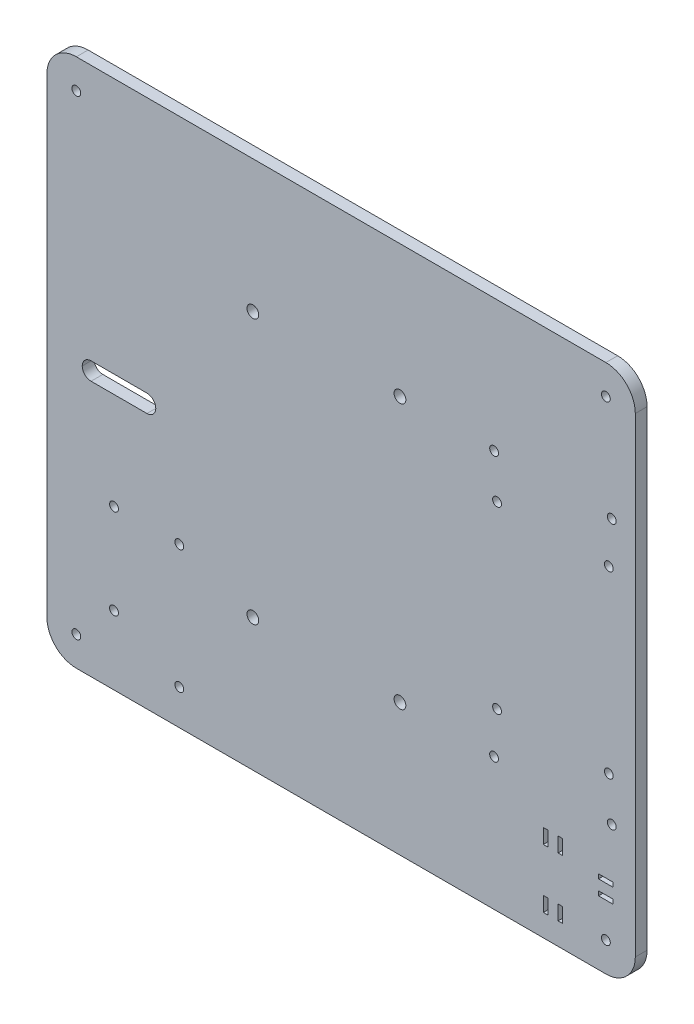
SolidWorks part; units mm, degrees
ref_plane "Front Plane" through (0, 0, 0) normal (0, 0, 1) x (1, 0, 0)
ref_plane "Top Plane" through (0, 0, 0) normal (0, 1, 0) x (1, 0, 0)
ref_plane "Right Plane" through (0, 0, 0) normal (1, 0, 0) x (0, 0, -1)
sketch "Sketch1" plane through (0, 0, 0) normal (0, 0, 1) x (1, 0, 0)
  line L0 (0, 0) -> (121.7014, 0) construction
  line L2 (105, 90) -> (-95, 90)
  line L3 (105, 90) -> (105, -90)
  line L4 (105, -90) -> (-95, -90)
  line L5 (-95, 90) -> (-95, -90)
  line L6 (105, 90) -> (-95, -90) construction
  line L7 (105, -90) -> (-95, 90) construction
  arc A0 (-28.7189, 34.6443) -> (-28.7189, -34.6443) centre (0, 0) ccw construction
  point P3 (5, 0)
  dimension "D1" = 180
  dimension "D2" = 50
  dimension "D3" = 53
  dimension "D4" = 200
extrude "Boss-Extrude1" add sketch "Sketch1" along normal blind 4
sketch "Sketch2" plane through (0, 0, 0) normal (0, 0, -1) x (-1, 0, 0)
  circle A0 centre (25, 45) radius 2 construction
  circle A1 centre (25, 45) radius 2
  circle A2 centre (-25, 45) radius 2 construction
  circle A3 centre (-25, 45) radius 2
  circle A4 centre (-25, -45) radius 2 construction
  circle A5 centre (-25, -45) radius 2
  circle A6 centre (25, -45) radius 2 construction
  circle A7 centre (25, -45) radius 2
extrude "Cut-Extrude1" cut sketch "Sketch2" against normal through all
fillet "Fillet1" radius 10 4 edges at (-95, -90, 2) (-95, 90, 2) (105, -90, 2) (105, 90, 2)
sketch "Sketch4" plane through (0, 0, 0) normal (0, 0, -1) x (-1, 0, 0)
  line L0 (-102, 0) -> (-52, 0) construction
  line L2 (-96, -30.5) -> (-58, -30.5) construction
  line L3 (-96, -30.5) -> (-96, 30.5) construction
  line L4 (-52, -36) -> (-52, 36)
  line L5 (-52, 36) -> (-102, 36)
  line L6 (-102, 36) -> (-102, -36)
  line L7 (-102, -36) -> (-52, -36)
  line L8 (-52, -36) -> (-52, 36) construction
  line L9 (-52, 36) -> (-102, 36) construction
  line L10 (-102, 36) -> (-102, -36) construction
  line L11 (-102, -36) -> (-52, -36) construction
  line L12 (-96, 30.5) -> (-58, 30.5) construction
  line L13 (-58, -30.5) -> (-58, 30.5) construction
  line L14 (-96, -30.5) -> (-58, 30.5) construction
  line L15 (-96, 30.5) -> (-58, -30.5) construction
  circle A0 centre (-96, 30.5) radius 1.5
  circle A1 centre (-58, 30.5) radius 1.5
  circle A2 centre (-96, -30.5) radius 1.5
  circle A3 centre (-58, -30.5) radius 1.5
  point P6 (-77, 0)
  dimension "D4" = 3
  dimension "D2" = 38
  dimension "D3" = 61
  dimension "D1" = 0
extrude "Cut-Extrude3" cut sketch "Sketch4" against normal blind 20
sketch "Sketch5" plane through (0, 0, 0) normal (0, 0, -1) x (-1, 0, 0)
  line L0 (-77, 36) -> (-77, -36) construction
  line L1 (-52, 36) -> (-102, 36) construction
  line L2 (-102, -36) -> (-52, -36) construction
  line L4 (-97, 45) -> (-57, 45) construction
  line L5 (-97, 45) -> (-97, -45) construction
  line L6 (-97, -45) -> (-57, -45) construction
  line L7 (-57, 45) -> (-57, -45) construction
  line L8 (-97, 45) -> (-57, -45) construction
  line L9 (-97, -45) -> (-57, 45) construction
  circle A0 centre (-57, 45) radius 1.5
  circle A1 centre (-97, 45) radius 1.5
  circle A2 centre (-97, -45) radius 1.5
  circle A3 centre (-57, -45) radius 1.5
  point P6 (-77, 0)
  dimension "D3" = 3
  dimension "D1" = 40
  dimension "D2" = 90
extrude "Cut-Extrude4" cut sketch "Sketch5" against normal through all
sketch "Sketch6" plane through (0, 0, 0) normal (0, 0, -1) x (-1, 0, 0)
  line L0 (-77, 36) -> (-77, -90) construction
  line L1 (-52, 36) -> (-102, 36) construction
  line L2 (85, -90) -> (-95, -90) construction
  line L3 (-92.2763, -65) -> (-105, -65) construction
  line L4 (-105, -80) -> (-105, 80) construction
  line L5 (-79.5, -60) -> (-79.5, -80) construction
  line L6 (-75.25, -57.5) -> (-73.75, -57.5)
  line L7 (-75.25, -57.5) -> (-75.25, -62.5)
  line L8 (-75.25, -62.5) -> (-73.75, -62.5)
  line L9 (-73.75, -57.5) -> (-73.75, -62.5)
  line L10 (-75.25, -57.5) -> (-73.75, -62.5) construction
  line L11 (-75.25, -62.5) -> (-73.75, -57.5) construction
  line L12 (-80.25, -57.5) -> (-78.75, -57.5)
  line L13 (-80.25, -57.5) -> (-80.25, -62.5)
  line L14 (-80.25, -62.5) -> (-78.75, -62.5)
  line L15 (-78.75, -57.5) -> (-78.75, -62.5)
  line L16 (-80.25, -57.5) -> (-78.75, -62.5) construction
  line L17 (-80.25, -62.5) -> (-78.75, -57.5) construction
  line L18 (-75.25, -77.5) -> (-73.75, -77.5)
  line L19 (-75.25, -77.5) -> (-75.25, -82.5)
  line L20 (-75.25, -82.5) -> (-73.75, -82.5)
  line L21 (-73.75, -77.5) -> (-73.75, -82.5)
  line L22 (-75.25, -77.5) -> (-73.75, -82.5) construction
  line L23 (-75.25, -82.5) -> (-73.75, -77.5) construction
  line L24 (-80.25, -77.5) -> (-78.75, -77.5)
  line L25 (-80.25, -77.5) -> (-80.25, -82.5)
  line L26 (-80.25, -82.5) -> (-78.75, -82.5)
  line L27 (-78.75, -77.5) -> (-78.75, -82.5)
  line L28 (-80.25, -77.5) -> (-78.75, -82.5) construction
  line L29 (-80.25, -82.5) -> (-78.75, -77.5) construction
  line L30 (-92.5, -66.75) -> (-97.5, -66.75)
  line L31 (-92.5, -66.75) -> (-92.5, -68.25)
  line L32 (-92.5, -68.25) -> (-97.5, -68.25)
  line L33 (-97.5, -66.75) -> (-97.5, -68.25)
  line L34 (-92.5, -66.75) -> (-97.5, -68.25) construction
  line L35 (-92.5, -68.25) -> (-97.5, -66.75) construction
  line L36 (-97.5, -61.75) -> (-92.5, -61.75)
  line L37 (-97.5, -61.75) -> (-97.5, -63.25)
  line L38 (-97.5, -63.25) -> (-92.5, -63.25)
  line L39 (-92.5, -61.75) -> (-92.5, -63.25)
  line L40 (-97.5, -61.75) -> (-92.5, -63.25) construction
  line L41 (-97.5, -63.25) -> (-92.5, -61.75) construction
  line L42 (-79.5, -80) -> (-74.5, -80) construction
  line L43 (-74.5, -80) -> (-74.5, -60) construction
  line L44 (-95, -62.5) -> (-95, -67.5) construction
  line L45 (-95, -62.5) -> (-98.7919, -62.5) construction
  point P10 (-74.5, -60)
  point P15 (-79.5, -60)
  point P20 (-74.5, -80)
  point P25 (-79.5, -80)
  point P30 (-95, -67.5)
  point P35 (-95, -62.5)
  dimension "D1" = 5
  dimension "D2" = 1.5
  dimension "D3" = 2.5
  dimension "D4" = 5
  dimension "D5" = 20
  dimension "D6" = 10
  dimension "D7" = 10
  dimension "D8" = 2.5
  dimension "D9" = 5
  dimension "D10" = 25
extrude "Cut-Extrude5" cut sketch "Sketch6" against normal through all
sketch "Sketch7" plane through (0, 0, 0) normal (0, 0, -1) x (-1, 0, 0)
  circle A0 centre (85, 80) radius 1.5
  circle A1 centre (85, -80) radius 1.5
  circle A2 centre (-95, -80) radius 1.5
  circle A3 centre (-95, 80) radius 1.5
  dimension "D1" = 3
extrude "Cut-Extrude6" cut sketch "Sketch7" against normal through all
sketch "Sketch8" plane through (0, 0, 0) normal (0, 0, -1) x (-1, 0, 0)
  circle A0 centre (72.2, -66.6) radius 1.55 construction
  circle A1 centre (72.2, -36) radius 1.55 construction
  circle A2 centre (50, -36) radius 1.6 construction
  circle A3 centre (50, -78) radius 1.6 construction
  circle A4 centre (72.2, -66.6) radius 1.55 construction
  circle A5 centre (72.2, -36) radius 1.55 construction
  circle A6 centre (50, -36) radius 1.6 construction
  circle A7 centre (50, -78) radius 1.6 construction
  circle A8 centre (50, -78) radius 1.5
  circle A9 centre (72.2, -66.6) radius 1.5
  circle A10 centre (72.2, -36) radius 1.5
  circle A11 centre (50, -36) radius 1.5
  dimension "D1" = 3
extrude "Cut-Extrude7" cut sketch "Sketch8" against normal through all
sketch "Sketch9" plane through (0, 0, 4) normal (0, 0, 1) x (1, 0, 0)
  line L4 (-58, -3) -> (-58, 3)
  line L5 (-83, -3) -> (-58, -3)
  line L6 (-83, 3) -> (-83, -3)
  line L7 (-58, 3) -> (-83, 3)
  line L8 (-58, -3) -> (-58, 3)
  line L9 (-83, -3) -> (-58, -3)
  line L10 (-83, 3) -> (-83, -3)
  line L11 (-58, 3) -> (-83, 3)
  dimension "D1" = 0
extrude "Cut-Extrude8" cut sketch "Sketch9" against normal blind 10
fillet "Fillet2" radius 3 4 edges at (-58, -3, 2) (-58, 3, 2) (-83, -3, 2) (-83, 3, 2)
